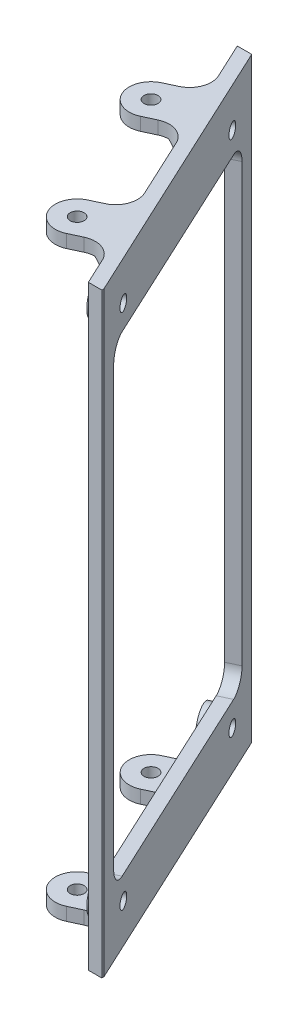
SolidWorks part; units mm, degrees
ref_plane "Plan de face" through (0, 0, 0) normal (0, 0, 1) x (1, 0, 0)
ref_plane "Plan de dessus" through (0, 0, 0) normal (0, 1, 0) x (1, 0, 0)
ref_plane "Plan de droite" through (0, 0, 0) normal (1, 0, 0) x (0, 0, -1)
sketch "Esquisse1" plane through (0, 0, 0) normal (0, 1, 0) x (1, 0, 0)
  line L1 (2.7189, 1.2679) -> (-26.8644, 64.7094)
  line L4 (2.7189, 1.2679) -> (0, 0)
  line L5 (0, 0) -> (-29.5833, 63.4415)
  line L6 (-29.5833, 63.4415) -> (-26.8644, 64.7094)
  line L7 (0, 0) -> (-27.4156, 0) construction
  line L9 (-26.8644, 64.7094) -> (-30.1745, 64.7094)
  line L10 (-30.1745, 64.7094) -> (-29.5833, 63.4415)
  line L11 (2.7189, 1.2679) -> (2.7189, 0.7679)
  line L12 (2.7189, 0.7679) -> (-0.3581, 0.7679)
  dimension "D1" = 70
  dimension "D2" = 65
  dimension "D3" = 3
  dimension "D4" = 0.5
extrude "Boss.-Extru.1" add sketch "Esquisse1" along normal mid plane 136.5 contours L1 L6 L5 | L9 L10 L6 | L12 L11 L4 region at (-13.4832, 0, -32.4718) region at (2.3615, 0, -0.9345) region at (-28.874, 0, -64.2868)
sketch "Esquisse2" plane through (2.7189, 0, -1.2679) normal (0.9063, 0, -0.4226) x (-0.4226, 0, -0.9063)
  line L0 (70, 68.25) -> (0, -68.25) construction
  line L8 (61.4, 54.025) -> (8.6, 54.025)
  line L9 (65.4, 50.025) -> (65.4, -50.025)
  line L10 (61.4, -54.025) -> (8.6, -54.025)
  line L11 (4.6, 50.025) -> (4.6, -50.025)
  line L12 (65.4, 54.025) -> (4.6, -54.025) construction
  line L13 (65.4, -54.025) -> (4.6, 54.025) construction
  line L14 (60.81, 59.31) -> (9.19, 59.31) construction
  line L15 (60.81, 59.31) -> (60.81, -59.31) construction
  line L16 (60.81, -59.31) -> (9.19, -59.31) construction
  line L17 (9.19, 59.31) -> (9.19, -59.31) construction
  line L18 (60.81, 59.31) -> (9.19, -59.31) construction
  line L19 (60.81, -59.31) -> (9.19, 59.31) construction
  arc A0 (65.4, -50.025) -> (61.4, -54.025) centre (61.4, -50.025) cw
  arc A1 (8.6, -54.025) -> (4.6, -50.025) centre (8.6, -50.025) cw
  arc A2 (8.6, 54.025) -> (4.6, 50.025) centre (8.6, 50.025) ccw
  arc A3 (61.4, 54.025) -> (65.4, 50.025) centre (61.4, 50.025) cw
  circle A4 centre (60.81, 59.31) radius 1.6
  circle A5 centre (9.19, 59.31) radius 1.6
  circle A6 centre (60.81, -59.31) radius 1.6
  circle A7 centre (9.19, -59.31) radius 1.6
  point P0 (35, 0)
  point P10 (35, 0)
  point P26 (35, 0)
  dimension "D5" = 4
  dimension "D6" = 3.2
  dimension "D3" = 108.05
  dimension "D4" = 60.8
  dimension "D7" = 118.62
  dimension "D8" = 51.62
extrude "Enlèv. mat.-Extru.2" cut sketch "Esquisse2" against normal through all contours L8 A2 L11 A1 L10 A0 L9 A3 | A4 | A5 | A7 | A6
sketch "Esquisse9" plane through (0, 0, 0) normal (-0.9063, 0, 0.4226) x (0.4226, 0, 0.9063)
  circle A0 centre (-9.19, 59.31) radius 1.6 construction
  circle A1 centre (-60.81, 59.31) radius 1.6 construction
  circle A2 centre (-9.19, -59.31) radius 1.6 construction
  circle A3 centre (-60.81, -59.31) radius 1.6 construction
  circle A4 centre (-9.19, 59.31) radius 1.6
  circle A5 centre (-60.81, 59.31) radius 1.6
  circle A6 centre (-9.19, -59.31) radius 1.6
  circle A7 centre (-60.81, -59.31) radius 1.6
  circle A8 centre (-60.81, -59.31) radius 3.6
  circle A9 centre (-9.19, -59.31) radius 3.6
  circle A10 centre (-60.81, 59.31) radius 3.6
  circle A11 centre (-9.19, 59.31) radius 3.6
  dimension "D1" = 2
extrude "Boss.-Extru.2" add sketch "Esquisse9" along normal blind 2
sketch "Esquisse12" plane through (0, 68.25, 0) normal (0, 1, 0) x (1, 0, 0)
  line L0 (-24.3048, 52.1219) -> (-20.0787, 43.0588)
  line L1 (-24.3048, 52.1219) -> (-36.0868, 46.6278)
  line L2 (-20.0787, 43.0588) -> (-31.8607, 37.5648)
  line L3 (-36.0868, 46.6278) -> (-31.8607, 37.5648)
  line L4 (-0.3581, 0.7679) -> (-30.1745, 64.7094) construction
  line L5 (-9.5132, 20.4011) -> (-5.287, 11.338)
  line L6 (-9.5132, 20.4011) -> (-21.2952, 14.9071)
  line L7 (-5.287, 11.338) -> (-17.069, 5.844)
  line L8 (-21.2952, 14.9071) -> (-17.069, 5.844)
  line L14 (-36.0868, 46.6278) -> (-22.7976, 41.791) construction
  line L15 (-21.2952, 14.9071) -> (-8.0059, 10.0702) construction
  line L17 (-29.4422, 44.2094) -> (-22.1917, 47.5903) construction
  line L18 (-14.6506, 12.4886) -> (-7.4001, 15.8696) construction
  line L20 (-26.8644, 64.7094) -> (-30.1745, 64.7094) construction
  circle A0 centre (-29.4422, 44.2094) radius 1.6
  circle A1 centre (-14.6506, 12.4886) radius 1.6
  dimension "D4" = 3.2
  dimension "D1" = 10
  dimension "D2" = 45
  dimension "D3" = 45
  dimension "D5" = 20.5
  dimension "D6" = 35
  dimension "D7" = 8
extrude "Boss.-Extru.4" add sketch "Esquisse12" against normal blind 3
mirror "Symétrie1" about plane through (0, 0, 0) normal (0, 1, 0) of "Boss.-Extru.4"
chamfer "Chanfrein1" distance 3 angle 45 4 edges at (-7.4001, 65.25, -15.8696) (-22.1917, 65.25, -47.5903) (-7.4001, -65.25, -15.8696) (-22.1917, -65.25, -47.5903)
fillet "Congé1" radius 5 16 edges at (-5.287, -65.25, -11.338) (-17.069, -66.75, -5.844) (-21.2952, -66.75, -14.9071) (-9.5132, -65.25, -20.4011) (-20.0787, -65.25, -43.0588) (-31.8607, -66.75, -37.5648) (-36.0868, -66.75, -46.6278) (-24.3048, -65.25, -52.1219) (-5.287, 65.25, -11.338) (-17.069, 66.75, -5.844) (-9.5132, 65.25, -20.4011) (-24.3048, 65.25, -52.1219) (-20.0787, 65.25, -43.0588) (-21.2952, 66.75, -14.9071) (-31.8607, 66.75, -37.5648) (-36.0868, 66.75, -46.6278)
